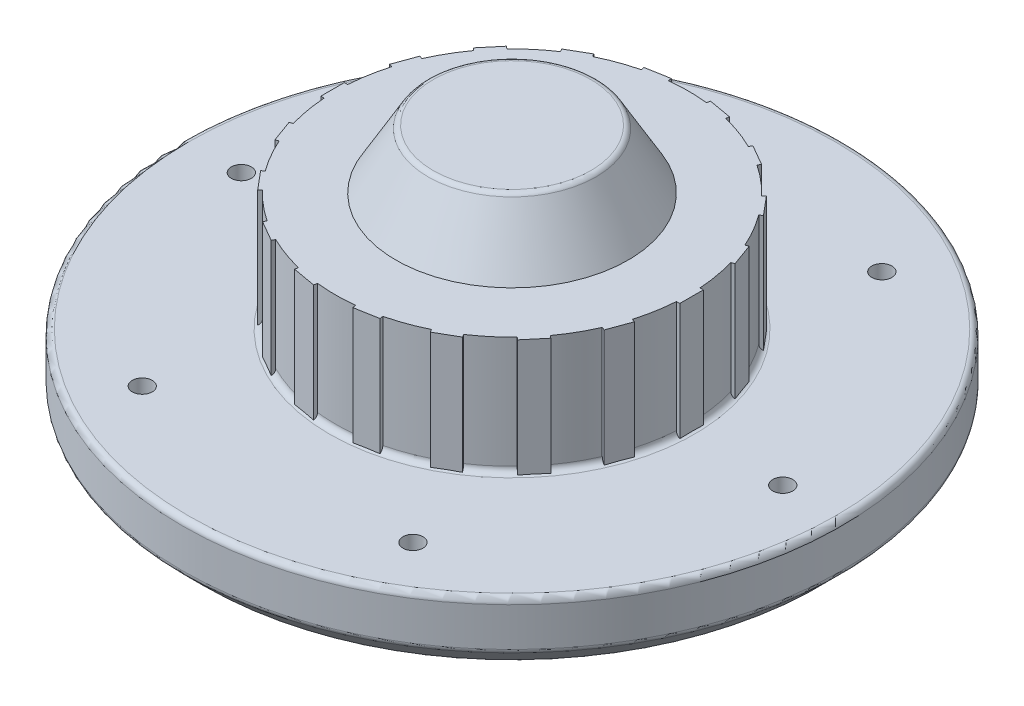
SolidWorks part; units mm, degrees
material "PET"
ref_plane "Front Plane" through (0, 0, 0) normal (0, 0, 1) x (1, 0, 0)
ref_plane "Top Plane" through (0, 0, 0) normal (0, 1, 0) x (1, 0, 0)
ref_plane "Right Plane" through (0, 0, 0) normal (1, 0, 0) x (0, 0, -1)
sketch "Sketch1" plane through (0, 0, 0) normal (0, 0, 1) x (1, 0, 0)
  line L0 (0, 0) -> (0, 42) construction
  line L1 (0, 42) -> (13.9765, 42)
  line L2 (13.9765, 42) -> (19.75, 32)
  line L3 (19.75, 32) -> (30, 32)
  line L4 (30, 32) -> (30, 12)
  line L5 (56, 12) -> (56, 4)
  line L6 (56, 4) -> (52, 0)
  line L7 (52, 0) -> (0, 0)
  line L8 (0, 0) -> (0, 42)
  line L9 (30, 12) -> (56, 12)
  dimension "D1" = 39.5
  dimension "D3" = 60
  dimension "D5" = 10
  dimension "D6" = 4
  dimension "D7" = 4
  dimension "D2" = 56
  dimension "D4" = 30
  dimension "D8" = 20
  dimension "D9" = 12
revolve "body" add sketch "Sketch1" angle 360 about L0
sketch "Sketch3" plane through (0, 0, 0) normal (0, -1, 0) x (1, 0, 0)
  point P0 (46, 0)
  dimension "D1" = 46
hole_wizard "socket_hole" positions "Sketch3" profile "Sketch4" counterbore size "M3" standard "DIN" end condition up to next
sketch "Sketch4" plane through (46, 0, 0) normal (1, 0, 0) x (0, 0, -1)
  line L0 (0, 0) -> (0, 12)
  line L1 (0, 12) -> (1.7, 12)
  line L3 (1.7, 12) -> (1.7, 8)
  line L4 (1.7, 8) -> (3.25, 8)
  line L5 (3.25, 8) -> (3.25, 0)
  line L7 (3.25, 0) -> (0, 0)
  line L11 (0, -6.35) -> (0, 107.95) construction
  dimension "Thru Hole Dia." = 3.4
  dimension "Thru Hole Depth" = 12
  dimension "C'Bore Dia." = 6.5
  dimension "C'Bore Depth" = 8
pattern_circular "socket_hole_pattern" count 6 over 360 about axis through (0, 0, 0) along (0, -1, 0) of "socket_hole"
fillet "overall_fillets" radius 1 11 edges at (23, 0, 36.5872) (46, 0, -3.25) (23, 0, -43.0872) (-23, 0, -43.0872) (-46, 0, -3.25) (-23, 0, 36.5872) (0, 4, -56) (0, 0, -52) (0, 42, -13.9765) (0, 12, -30) (0, 12, -56)
sketch "Sketch6" plane through (0, 32, 0) normal (0, 1, 0) x (1, 0, 0)
  line L1 (29.5, -2) -> (30.5, -2)
  line L2 (29.5, -2) -> (29.5, 2)
  line L3 (29.5, 2) -> (30.5, 2)
  line L4 (30.5, -2) -> (30.5, 2)
  line L5 (29.5, -2) -> (30.5, 2) construction
  line L6 (29.5, 2) -> (30.5, -2) construction
  circle A0 centre (0, 0) radius 30 construction
  point P0 (30, 0)
  dimension "D1" = 1
  dimension "D2" = 4
extrude "side_extrusion" add sketch "Sketch6" against normal up to next
pattern_circular "side_extrusion_pattern" count 18 over 360 about axis through (0, 32, 0) along (0, -1, 0) of "side_extrusion"
equation "\"paper_size\" = 600mm"
equation "\"cb_roll_d_outer\" = 86mm"
equation "\"cb_roll_d_inner\" = 76mm"
equation "\"attached_len\" = \"spring_l_max\" * 2 - \"spring_l_min\" + 18"
equation "\"helper_d\" = 92mm"
equation "\"outer_d\" = 112mm"
equation "\"spring_l_max\" = 25mm"
equation "\"spring_l_min\" = 10mm"
equation "\"cone_d_larger\" = 40mm"
equation "\"cone_angle\" = 60deg"
equation "\"D1@Sketch1\"=\"cone_d_larger\" - 0.5"
equation "\"D3@Sketch1\"=\"cone_angle\""
equation "\"D2@Sketch1\"=\"outer_d\" / 2"
equation "\"bottom_screw_ring_d\" = 92mm"
equation "\"D1@Sketch3\"=\"bottom_screw_ring_d\" / 2"
